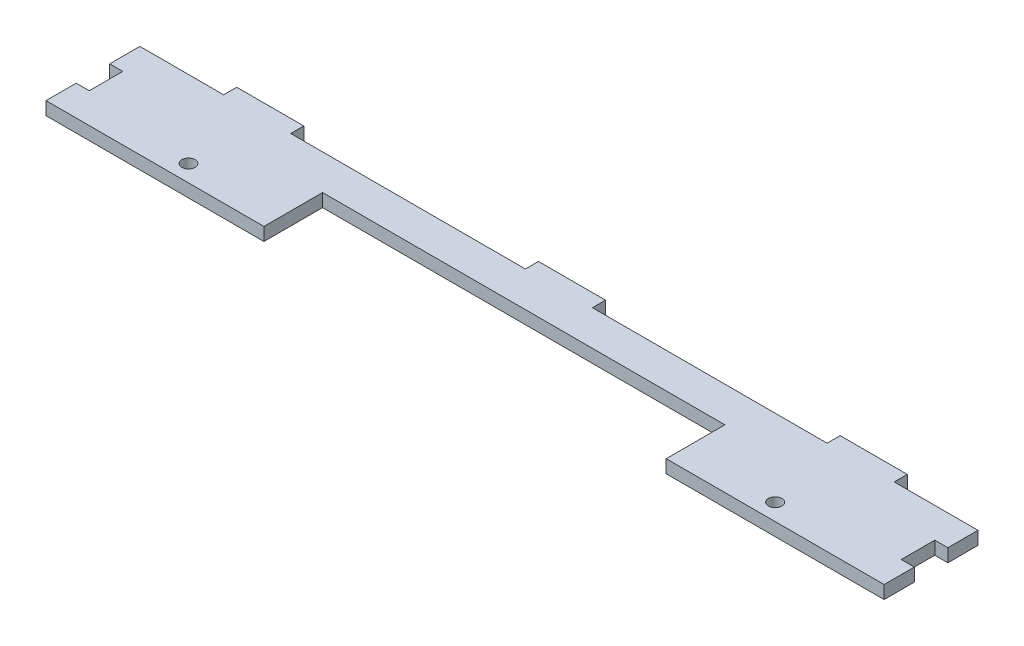
SolidWorks part; units mm, degrees
material "Very Low Density PE (SS)"
ref_plane "Front Plane" through (0, 0, 0) normal (0, 0, 1) x (1, 0, 0)
ref_plane "Top Plane" through (0, 0, 0) normal (0, 1, 0) x (1, 0, 0)
ref_plane "Right Plane" through (0, 0, 0) normal (1, 0, 0) x (0, 0, -1)
sketch "Sketch1" plane through (0, 0, 0) normal (0, 1, 0) x (1, 0, 0)
  line L0 (0, -14) -> (0, 15.95) construction
  line L1 (-125, 14) -> (-100, 14)
  line L2 (-125, 14) -> (-125, 5)
  line L3 (-125, -14) -> (125, -14)
  line L4 (125, 14) -> (125, 5)
  line L5 (-125, 14) -> (125, -14) construction
  line L6 (-125, -14) -> (125, 14) construction
  line L7 (100, 17.9) -> (80, 17.9)
  line L9 (-100, 14) -> (-100, 17.9)
  line L10 (-100, 17.9) -> (-80, 17.9)
  line L11 (-80, 14) -> (-80, 17.9)
  line L12 (80, 14) -> (80, 17.9)
  line L14 (100, 14) -> (100, 17.9)
  line L15 (-80, 14) -> (-10, 14)
  line L16 (100, 14) -> (125, 14)
  line L17 (10, 14) -> (80, 14)
  line L18 (-10, 17.9) -> (10, 17.9)
  line L19 (-10, 17.9) -> (-10, 14)
  line L21 (10, 17.9) -> (10, 14)
  line L22 (-10, 17.9) -> (10, 14) construction
  line L23 (-10, 14) -> (10, 17.9) construction
  line L24 (-125, -9) -> (125, -9) construction
  line L25 (121.1, 5) -> (125, 5)
  line L26 (-121.1, -5) -> (-125, -5)
  line L27 (-121.1, -5) -> (-121.1, 5)
  line L28 (-121.1, 5) -> (-125, 5)
  line L29 (-125, -5) -> (-125, 5) construction
  line L30 (-121.1, -5) -> (-125, 5) construction
  line L31 (-121.1, 5) -> (-125, -5) construction
  line L32 (125, -5) -> (125, 5) construction
  line L33 (121.1, -5) -> (125, -5)
  line L34 (121.1, -5) -> (121.1, 5)
  line L35 (-125, 5) -> (-125, -5) construction
  line L36 (-125, -5) -> (-125, -14)
  line L37 (125, 5) -> (125, -5) construction
  line L38 (125, -5) -> (125, -14)
  line L39 (-60, -14) -> (-60, 3.5)
  line L40 (-60, 3.5) -> (60, 3.5)
  line L41 (60, -14) -> (60, 3.5)
  circle A0 centre (-30, -9) radius 2
  circle A1 centre (-87.5, -9) radius 2
  circle A2 centre (30, -9) radius 2
  circle A3 centre (87.5, -9) radius 2
  point P0 (0, 0)
  point P18 (0, 15.95)
  point P31 (-123.05, 0)
  point P42 (-12.5058, 3.5)
  point P46 (0, 3.5)
  dimension "D8" = 4
  dimension "D10" = 4
  dimension "D12" = 10
  dimension "D1" = 250
  dimension "D2" = 28
  dimension "D3" = 20
  dimension "D4" = 3.9
  dimension "D5" = 25
  dimension "D6" = 20
  dimension "D7" = 5
  dimension "D9" = 30
  dimension "D11" = 87.5
  dimension "D13" = 3.9
  dimension "D14" = 17.5
  dimension "D15" = 60
extrude "Boss-Extrude1" add sketch "Sketch1" along normal blind 3.9 contours L41 L3 L38 L33 L34 L25 L4 L16 L14 L7 L12 L17 L21 L18 L19 L15 L11 L10 L9 L1 L2 L28 L27 L26 L36 L39 L40 A1 A3 region at (-112.5, 0, -11.4797)
